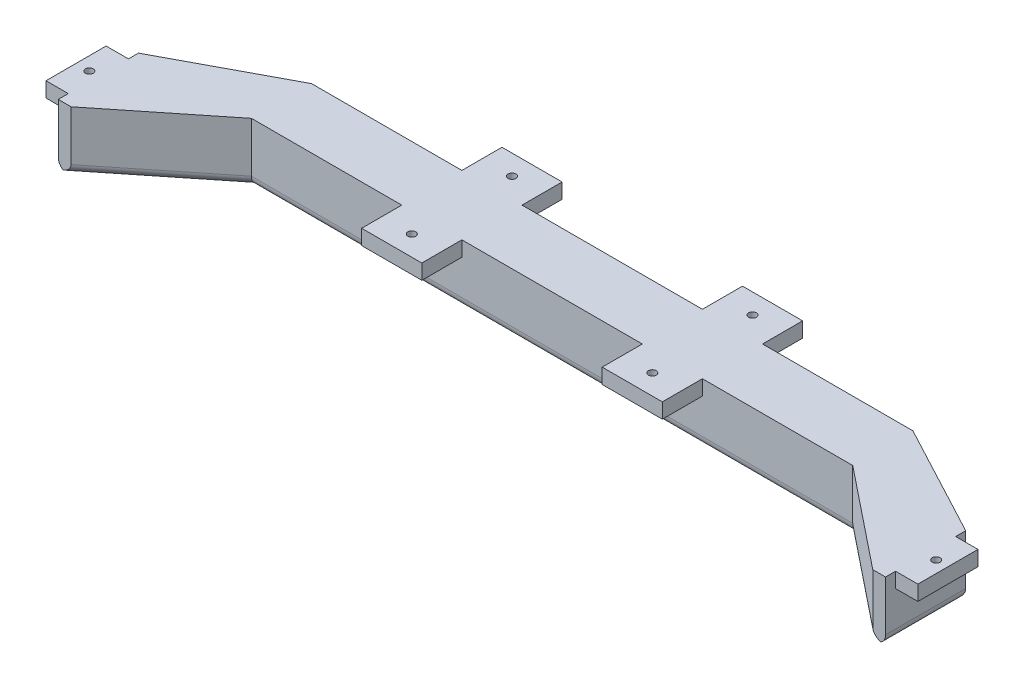
SolidWorks part; units mm, degrees
material "Galvanized Steel"
ref_plane "Front Plane" through (0, 0, 0) normal (0, 0, 1) x (1, 0, 0)
ref_plane "Top Plane" through (0, 0, 0) normal (0, 1, 0) x (1, 0, 0)
ref_plane "Right Plane" through (0, 0, 0) normal (1, 0, 0) x (0, 0, -1)
sketch "Sketch1" plane through (0, 0, 0) normal (0, 0, 1) x (1, 0, 0)
  line L0 (1524, 152.4) -> (0, 152.4)
  line L1 (0, 0) -> (1524, 0)
  line L2 (0, 0) -> (0, 152.4)
  line L4 (1524, 0) -> (1524, 152.4)
  dimension "D1" = 1524
  dimension "D2" = 152.4
extrude "Boss-Extrude1" add sketch "Sketch1" along normal blind 152.4
sketch "Sketch8" plane through (0, 152.4, 0) normal (0, 1, 0) x (1, 0, 0)
  line L0 (0, -152.4) -> (-254, -355.6)
  line L1 (-254, -355.6) -> (-286.3565, -355.6)
  line L2 (-286.3565, -355.6) -> (-286.3565, -152.4)
  line L3 (-286.3565, -152.4) -> (0, 0)
  line L5 (0, -152.4) -> (0, 0)
  dimension "D1" = 286.3565
  dimension "D2" = 203.2
  dimension "D3" = 203.2
  dimension "D4" = 254
extrude "Boss-Extrude2" add sketch "Sketch8" against normal blind 152.4
ref_plane "Plane3" through (762, 0, 0) normal (1, 0, 0) x (0, 0, -1)
ref_plane "Plane1" through (762, 0, 0) normal (1, 0, 0) x (0, 0, -1)
mirror "Mirror1" about plane through (762, 0, 0) normal (1, 0, 0) of "Boss-Extrude2"
fillet "Fillet1" radius 25.4 8 edges at (-143.1782, 0, 76.2) (-286.3565, 0, 254) (-127, 0, 254) (762, 0, 152.4) (1651, 0, 254) (1810.3565, 0, 254) (1667.1782, 0, 76.2) (762, 0, 0)
sketch "Sketch9" plane through (0, 0, 0) normal (0, 0, -1) x (-1, 0, 0)
  line L0 (-381, 152.4) -> (-381, 114.3)
  line L1 (-1524, 152.4) -> (0, 152.4) construction
  line L2 (-381, 114.3) -> (-533.4, 114.3)
  line L3 (-533.4, 114.3) -> (-533.4, 152.4)
  line L4 (-533.4, 152.4) -> (-381, 152.4)
  line L5 (-990.6, 152.4) -> (-990.6, 114.3)
  line L6 (-990.6, 114.3) -> (-1143, 114.3)
  line L7 (-1143, 114.3) -> (-1143, 152.4)
  line L8 (-1143, 152.4) -> (-990.6, 152.4)
  line L9 (-1524, 25.4) -> (-1524, 152.4) construction
  line L10 (0, 152.4) -> (0, 25.4) construction
  dimension "D1" = 381
  dimension "D2" = 381
  dimension "D3" = 152.4
  dimension "D4" = 38.1
  dimension "D5" = 38.1
  dimension "D6" = 152.4
extrude "Boss-Extrude3" add sketch "Sketch9" along normal blind 101.6
sketch "Sketch11" plane through (-286.3565, 0, 0) normal (-1, 0, 0) x (0, 0, 1)
  line L0 (177.8, 152.4) -> (177.8, 114.3)
  line L1 (152.4, 152.4) -> (355.6, 152.4) construction
  line L2 (177.8, 114.3) -> (330.2, 114.3)
  line L3 (330.2, 114.3) -> (330.2, 152.4)
  line L5 (355.6, 25.4) -> (355.6, 152.4) construction
  line L7 (177.8, 152.4) -> (330.2, 152.4)
  dimension "D1" = 152.4
  dimension "D2" = 25.4
  dimension "D3" = 38.1
extrude "Boss-Extrude4" add sketch "Sketch11" along normal blind 56.515
mirror "Mirror3" about plane through (762, 0, 0) normal (1, 0, 0) of "Boss-Extrude4"
ref_plane "Plane4" through (0, 0, 76.2) normal (0, 0, 1) x (1, 0, 0)
mirror "Mirror4" about plane through (0, 0, 76.2) normal (0, 0, 1) of "Boss-Extrude3"
hole_wizard "#0000 Clearance Hole1" positions "Sketch12" profile "Sketch13" hole size "#0000" standard "ANSI Inch"
sketch "Sketch12" plane through (0, 0, 0) normal (0, -1, 0) x (-1, 0, 0)
  line L1 (260.9565, -328.6373) -> (260.9565, -167.6552) construction
  line L2 (260.9565, -167.6552) -> (-6.3381, -25.4) construction
  line L3 (-6.3381, -25.4) -> (-1517.6619, -25.4) construction
  line L6 (-1784.9565, -167.6552) -> (-1784.9565, -328.6373) construction
  point P0 (222.8565, -231.1552)
  point P4 (19.6565, -82.3942)
  point P6 (-175.9235, -76.2)
  point P8 (-371.5035, -76.2)
  point P10 (-567.0835, -76.2)
  point P12 (-762.0285, -76.2)
  point P14 (-956.9165, -76.2)
  point P16 (-1152.4965, -76.2)
  point P18 (-1348.0765, -76.2)
  point P20 (-1543.6565, -76.2)
  point P24 (-1746.8565, -231.1552)
  point P32 (260.9565, -248.1463)
  dimension "D1" = 38.1
  dimension "D2" = 63.5
  dimension "D5" = 38.1
  dimension "D6" = 241.3
  dimension "D7" = 50.8
  dimension "D8" = 50.8
  dimension "D9" = 50.8
  dimension "D10" = 50.8
  dimension "D11" = 50.8
  dimension "D12" = 50.8
  dimension "D13" = 50.8
  dimension "D14" = 50.8
  dimension "D16" = 38.1
  dimension "D18" = 63.5
  dimension "D19" = 241.3
  dimension "D20" = 195.58
  dimension "D21" = 195.58
  dimension "D22" = 195.58
  dimension "D23" = 195.58
  dimension "D24" = 195.58
  dimension "D25" = 195.58
  dimension "D26" = 194.945
sketch "Sketch13" plane through (-222.8565, 0, 231.1552) normal (1, 0, 0) x (0, 0, -1)
  line L0 (0, 0) -> (0, 15.0656)
  line L1 (0, 15.0656) -> (3.937, 12.7)
  line L2 (3.937, 12.7) -> (3.937, 0)
  line L5 (3.937, 0) -> (0, 0)
  line L10 (0, 15.0656) -> (-3.937, 12.7) construction
  line L11 (0, -6.35) -> (0, 107.95) construction
  dimension "Hole Dia." = 7.874
  dimension "Hole Depth" = 12.7
  dimension "Drill Angle" = 118
hole_wizard "CBORE for 3/4 Hex Head Bolt1" positions "Sketch15" profile "Sketch16" counterbore size "3/4" standard "ANSI Inch" end condition through all
sketch "Sketch15" plane through (0, 114.3, 0) normal (0, -1, 0) x (-1, 0, 0)
  line L1 (342.8715, -177.8) -> (286.3565, -177.8) construction
  line L2 (-1866.8715, -177.8) -> (-1810.3565, -177.8) construction
  line L4 (286.3565, -177.8) -> (286.3565, -330.2) construction
  line L6 (-533.4, 101.6) -> (-533.4, 0) construction
  line L7 (-533.4, -254) -> (-533.4, -152.4) construction
  line L8 (-533.4, 101.6) -> (-381, 101.6) construction
  line L9 (-533.4, -254) -> (-381, -254) construction
  line L10 (-1143, 101.6) -> (-990.6, 101.6) construction
  line L11 (-1143, 101.6) -> (-1143, 0) construction
  line L12 (-990.6, -254) -> (-990.6, -152.4) construction
  line L13 (-1143, -254) -> (-990.6, -254) construction
  point P0 (-457.2, 50.8)
  point P2 (-457.2, -203.2)
  point P4 (-1066.8, 50.8)
  point P6 (-1066.8, -203.2)
  point P8 (-1837.0835, -254)
  point P10 (309.2165, -254)
  dimension "D1" = 76.2
  dimension "D2" = 76.2
  dimension "D3" = 2146.3
  dimension "D4" = 22.86
  dimension "D5" = 76.2
  dimension "D6" = 76.2
  dimension "D7" = 50.8
  dimension "D8" = 50.8
  dimension "D9" = 50.8
  dimension "D10" = 76.2
  dimension "D11" = 76.2
  dimension "D12" = 50.8
sketch "Sketch16" plane through (457.2, 114.3, -50.8) normal (1, 0, 0) x (0, 0, -1)
  line L0 (0, 0) -> (0, 38.1)
  line L1 (0, 38.1) -> (9.9212, 38.1)
  line L3 (9.9212, 38.1) -> (9.9212, 13.3096)
  line L4 (9.9212, 13.3096) -> (20.6375, 13.3096)
  line L5 (20.6375, 13.3096) -> (20.6375, 0)
  line L7 (20.6375, 0) -> (0, 0)
  line L11 (0, -6.35) -> (0, 107.95) construction
  dimension "Thru Hole Dia." = 19.8425
  dimension "Thru Hole Depth" = 38.1
  dimension "C'Bore Dia." = 41.275
  dimension "C'Bore Depth" = 13.3096
